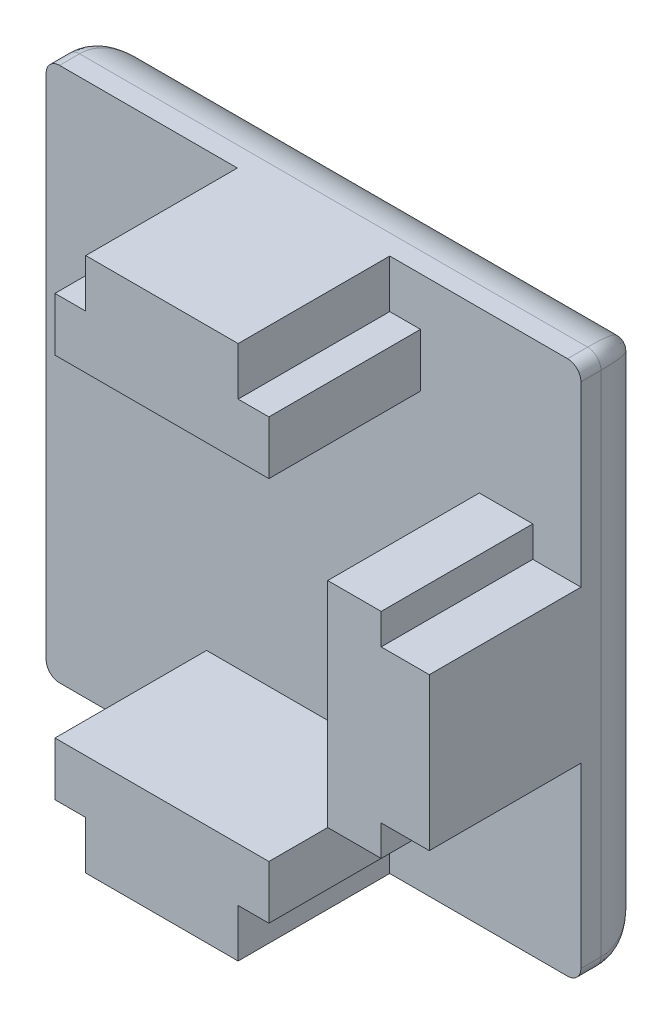
SolidWorks part; units mm, degrees
material "ABS"
ref_plane "Front Plane" through (0, 0, 0) normal (0, 0, 1) x (1, 0, 0)
ref_plane "Top Plane" through (0, 0, 0) normal (0, 1, 0) x (1, 0, 0)
ref_plane "Right Plane" through (0, 0, 0) normal (1, 0, 0) x (0, 0, -1)
sketch "Sketch1" plane through (0, 0, 0) normal (0, 0, 1) x (1, 0, 0)
  line L1 (-10, -10) -> (10, -10)
  line L2 (-10, -10) -> (-10, 10)
  line L3 (-10, 10) -> (10, 10)
  line L4 (10, -10) -> (10, 10)
  line L5 (-10, -10) -> (10, 10) construction
  line L6 (-10, 10) -> (10, -10) construction
  point P0 (0, 0)
  dimension "D1" = 20
extrude "Boss-Extrude1" add sketch "Sketch1" along normal blind 3
fillet "Fillet1" radius 0.5 4 edges at (10, -10, 1.5) (-10, -10, 1.5) (10, 10, 1.5) (-10, 10, 1.5)
fillet "Fillet2" radius 2.25 8 edges at (9.8536, 9.8536, 0) (0, 10, 0) (-9.8536, 9.8536, 0) (-10, 0, 0) (-9.8536, -9.8536, 0) (0, -10, 0) (9.8536, -9.8536, 0) (10, 0, 0)
sketch "Sketch2" plane through (0, 0, 3) normal (0, 0, 1) x (1, 0, 0)
  line L0 (-2.85, 10) -> (-2.85, 8.2)
  line L1 (9.5, 10) -> (-9.5, 10) construction
  line L2 (-2.85, 8.2) -> (-4, 8.2)
  line L3 (-4, 8.2) -> (-4, 6.2)
  line L4 (-4, 6.2) -> (4, 6.2)
  line L5 (4, 6.2) -> (4, 8.2)
  line L6 (4, 8.2) -> (2.85, 8.2)
  line L7 (2.85, 8.2) -> (2.85, 10)
  line L8 (2.85, 10) -> (-2.85, 10)
  line L9 (10, 2.85) -> (10, -2.85)
  line L10 (10, -9.5) -> (10, 9.5) construction
  line L11 (10, -2.85) -> (8.2, -2.85)
  line L12 (8.2, -2.85) -> (8.2, -4)
  line L13 (8.2, -4) -> (6.2, -4)
  line L14 (6.2, -4) -> (6.2, 4)
  line L15 (6.2, 4) -> (8.2, 4)
  line L16 (8.2, 4) -> (8.2, 2.85)
  line L17 (8.2, 2.85) -> (10, 2.85)
  line L18 (0, 6.2) -> (0, 0) construction
  line L19 (0, 0) -> (6.2, 0) construction
  line L20 (2.85, -10) -> (-2.85, -10)
  line L21 (2.85, -8.2) -> (2.85, -10)
  line L22 (4, -8.2) -> (2.85, -8.2)
  line L23 (4, -6.2) -> (4, -8.2)
  line L24 (-4, -6.2) -> (4, -6.2)
  line L25 (-4, -8.2) -> (-4, -6.2)
  line L26 (-2.85, -8.2) -> (-4, -8.2)
  line L27 (-2.85, -10) -> (-2.85, -8.2)
  dimension "D1" = 2
  dimension "D2" = 1.15
  dimension "D3" = 1.8
  dimension "D4" = 5.7
extrude "Boss-Extrude2" add sketch "Sketch2" along normal blind 5.67
